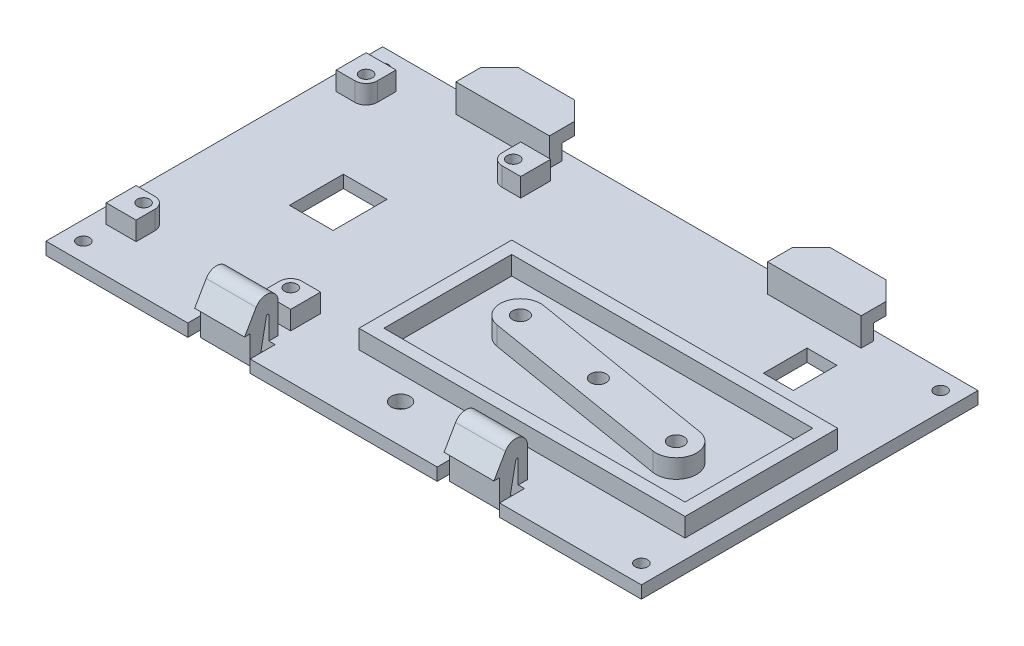
SolidWorks part; units mm, degrees
ref_plane "Front Plane" through (0, 0, 0) normal (0, 0, 1) x (1, 0, 0)
ref_plane "Top Plane" through (0, 0, 0) normal (0, 1, 0) x (1, 0, 0)
ref_plane "Right Plane" through (0, 0, 0) normal (1, 0, 0) x (0, 0, -1)
sketch "Sketch1" plane through (0, 0, 0) normal (0, 1, 0) x (1, 0, 0)
  line L1 (-47.75, 27) -> (47.75, 27)
  line L2 (-47.75, 27) -> (-47.75, -27)
  line L3 (-47.75, -27) -> (47.75, -27)
  line L4 (47.75, 27) -> (47.75, -27)
  line L5 (-47.75, 27) -> (47.75, -27) construction
  line L6 (-47.75, -27) -> (47.75, 27) construction
  point P0 (0, 0)
  dimension "D1" = 95.5
  dimension "D2" = 54
extrude "Boss-Extrude1" add sketch "Sketch1" along normal blind 2
sketch "Sketch5" plane through (0, 0, 0) normal (0, -1, 0) x (1, 0, 0)
  line L1 (-46.985, -26.185) -> (46.985, -26.185) construction
  line L2 (-46.985, -26.185) -> (-46.985, 26.185) construction
  line L3 (-46.985, 26.185) -> (46.985, 26.185) construction
  line L4 (46.985, -26.185) -> (46.985, 26.185) construction
  line L5 (-46.985, -26.185) -> (46.985, 26.185) construction
  line L6 (-46.985, 26.185) -> (46.985, -26.185) construction
  line L8 (-45.9867, -25.1841) -> (45.9867, -25.1841) construction
  line L9 (-45.9867, -25.1841) -> (-45.9867, 25.1841) construction
  line L10 (-45.9867, 25.1841) -> (45.9867, 25.1841) construction
  line L11 (45.9867, -25.1841) -> (45.9867, 25.1841) construction
  line L12 (-45.9867, -25.1841) -> (45.9867, 25.1841) construction
  line L13 (-45.9867, 25.1841) -> (45.9867, -25.1841) construction
  point P0 (0, 0)
  point P8 (0, 0)
  dimension "D1" = 93.97
  dimension "D2" = 52.37
  dimension "D3" = 91.9734
  dimension "D4" = 50.3682
sketch "Sketch2" plane through (0, 2, 0) normal (0, -1, 0) x (1, 0, 0)
  line L0 (0, 0) -> (0, -6.5874) construction
  line L1 (-32.5, -23.5) -> (-17.5, -23.5)
  line L2 (-32.5, -23.5) -> (-32.5, -25.5)
  line L3 (-32.5, -25.5) -> (-17.5, -25.5)
  line L4 (-17.5, -23.5) -> (-17.5, -25.5)
  line L5 (-32.5, -23.5) -> (-17.5, -25.5) construction
  line L6 (-32.5, -25.5) -> (-17.5, -23.5) construction
  line L7 (47.75, -27) -> (-47.75, -27) construction
  line L8 (32.5, -25.5) -> (17.5, -23.5) construction
  line L9 (32.5, -23.5) -> (17.5, -25.5) construction
  line L10 (17.5, -23.5) -> (17.5, -25.5)
  line L11 (32.5, -25.5) -> (17.5, -25.5)
  line L12 (32.5, -23.5) -> (32.5, -25.5)
  line L13 (32.5, -23.5) -> (17.5, -23.5)
  point P0 (-25, -24.5)
  point P16 (25, -24.5)
  dimension "D1" = 15
  dimension "D2" = 1.5
  dimension "D3" = 2
  dimension "D4" = 25
extrude "Boss-Extrude2" add sketch "Sketch2" against normal blind 2.5
sketch "Sketch3" plane through (0, 4.5, 0) normal (0, 1, 0) x (-1, 0, 0)
  line L0 (-32.5, -23.5) -> (-17.5, -23.5)
  line L1 (-17.5, -23.5) -> (-17.5, -30.5)
  line L2 (-17.5, -30.5) -> (-32.5, -30.5)
  line L3 (-32.5, -30.5) -> (-32.5, -23.5)
  line L4 (0, 0) -> (0, -9.2174) construction
  line L5 (17.5, -30.5) -> (32.5, -30.5)
  line L6 (17.5, -23.5) -> (17.5, -30.5)
  line L7 (32.5, -23.5) -> (17.5, -23.5)
  line L8 (32.5, -30.5) -> (32.5, -23.5)
  line L9 (-17.5, -23.5) -> (-17.5, -25.5) construction
  dimension "D1" = 7
extrude "Boss-Extrude3" add sketch "Sketch3" along normal blind 2
chamfer "Chamfer1" distance 3 angle 45 4 edges at (32.5, 5.5, -30.5) (17.5, 5.5, -30.5) (-17.5, 5.5, -30.5) (-32.5, 5.5, -30.5)
sketch "Sketch4" plane through (0, 0, 0) normal (0, -1, 0) x (1, 0, 0)
  line L0 (-47.75, 27) -> (47.75, 27) construction
  line L1 (-25, 23) -> (-15, 23)
  line L2 (-25, 23) -> (-25, 27)
  line L3 (-25, 27) -> (-15, 27)
  line L4 (-15, 23) -> (-15, 27)
  line L5 (-25, 23) -> (-15, 27) construction
  line L6 (-25, 27) -> (-15, 23) construction
  line L7 (0, 0) -> (0, 12.8978) construction
  line L8 (25, 27) -> (15, 23) construction
  line L9 (25, 23) -> (15, 27) construction
  line L10 (15, 23) -> (15, 27)
  line L11 (25, 27) -> (15, 27)
  line L12 (25, 23) -> (25, 27)
  line L13 (25, 23) -> (15, 23)
  point P0 (-20, 25)
  point P15 (20, 25)
  dimension "D1" = 10
  dimension "D2" = 4
  dimension "D3" = 20
extrude "Cut-Extrude1" cut sketch "Sketch4" against normal up to next
ref_plane "Plane1" through (-20, 0, 0) normal (1, 0, 0) x (0, 0, -1)
sketch "Sketch6" plane through (-20, 0, 0) normal (1, 0, 0) x (0, 0, -1)
  line L0 (-21.5, 2) -> (-21.5, 8.6569)
  line L1 (-27, 2) -> (27, 2) construction
  line L2 (-21.5, 8.6569) -> (-24.5, 8.6569)
  line L3 (-24.5, 8.6569) -> (-26, 6.0588)
  line L4 (-26.9, 4.5) -> (-26, 4.5)
  line L5 (-26, 4.5) -> (-26, 0)
  line L9 (-23, 7.6569) -> (-23, 2)
  line L10 (-23, 2) -> (-21.5, 2)
  line L12 (-27, 2) -> (-27, 0) construction
  line L13 (-27, 0) -> (27, 0) construction
  line L14 (-26, 6.0588) -> (-26.9, 4.5)
  line L15 (-24.5, 0) -> (-23, 7.6569)
  line L18 (-26, 0) -> (-24.5, 0)
  line L19 (-26.9, 4.5) -> (-26.9, 2) construction
  point P4 (-23, 8.6569)
  dimension "D1" = 1.5
  dimension "D2" = 60
  dimension "D3" = 1.5
  dimension "D4" = 2.5
  dimension "D5" = 1
  dimension "D6" = 0.1
  dimension "D8" = 1
extrude "Boss-Extrude4" add sketch "Sketch6" along normal mid plane 8
fillet "Fillet1" 2 edges at (-20, 8.6569, 24.5) (-20, 8.6569, 21.5) type full round first side face at (-20, 6.5785, 25.7) second side face at (-20, 5.3285, 21.5) middle face at (-20, 8.6569, 23)
fillet "Fillet2" radius 0.2 1 edges at (-20, 7.6569, 23)
mirror "Mirror1" about plane through (0, 0, 0) normal (1, 0, 0) of "Fillet2", "Fillet1", "Boss-Extrude4"
sketch "Sketch12" plane through (0, 2, 0) normal (0, 1, 0) x (1, 0, 0)
  line L0 (-47.75, -27) -> (-25, -27) construction
  line L1 (-47.75, 27) -> (-47.75, -27) construction
  line L2 (0, 6.8487) -> (0, 0) construction
  line L3 (0, 0) -> (6.5878, 0) construction
  line L6 (-45.9867, -25.1841) -> (45.9867, -25.1841) construction
  line L7 (45.9867, 25.1841) -> (45.9867, -25.1841) construction
  circle A0 centre (2.9867, -20.8641) radius 1.5
  circle A1 centre (-44.75, -24) radius 1
  circle A2 centre (44.75, -24) radius 1
  circle A3 centre (-44.75, 24) radius 1
  circle A4 centre (44.75, 24) radius 1
  dimension "D1" = 2
  dimension "D6" = 3
  dimension "D2" = 3
  dimension "D3" = 3
  dimension "D4" = 43
  dimension "D5" = 4.32
extrude "Cut-Extrude5" cut sketch "Sketch12" against normal up to next
sketch "Sketch13" plane through (0, 2, 0) normal (0, 1, 0) x (1, 0, 0)
  line L0 (45.9867, 25.1841) -> (45.9867, -25.1841) construction
  line L1 (28.1407, 19.1841) -> (32.9407, 19.1841)
  line L2 (28.1407, 19.1841) -> (28.1407, 12.1841)
  line L3 (28.1407, 12.1841) -> (32.9407, 12.1841)
  line L4 (32.9407, 19.1841) -> (32.9407, 12.1841)
  line L5 (28.1407, 19.1841) -> (32.9407, 12.1841) construction
  line L6 (28.1407, 12.1841) -> (32.9407, 19.1841) construction
  line L7 (-45.9867, 25.1841) -> (45.9867, 25.1841) construction
  point P0 (30.5407, 15.6841)
  dimension "D1" = 15.446
  dimension "D2" = 9.5
  dimension "D3" = 7
  dimension "D4" = 4.8
extrude "Cut-Extrude6" cut sketch "Sketch13" against normal up to next
sketch "Sketch8" plane through (0, 0, 0) normal (0, -1, 0) x (1, 0, 0)
  line L0 (-43.75, -17.35) -> (-43.75, -20.35) construction
  line L1 (-44.75, 19.75) -> (-16.15, 19.75) construction
  line L2 (-44.75, 19.75) -> (-44.75, -21.75) construction
  line L3 (-44.75, -21.75) -> (-16.15, -21.75) construction
  line L4 (-16.15, 19.75) -> (-16.15, -21.75) construction
  line L5 (-44.75, 19.75) -> (-16.15, -21.75) construction
  line L6 (-44.75, -21.75) -> (-16.15, 19.75) construction
  line L7 (-43.75, -20.35) -> (-40.75, -20.35) construction
  line L8 (-30.45, -6.366) -> (-30.45, -1) construction
  line L9 (-30.45, -1) -> (-27.7524, -1) construction
  line L10 (-17.15, -20.35) -> (-20.15, -20.35) construction
  line L11 (-17.15, -17.35) -> (-17.15, -20.35) construction
  line L12 (-43.75, 15.35) -> (-43.75, 18.35) construction
  line L13 (-43.75, 18.35) -> (-40.75, 18.35) construction
  line L14 (-17.15, 18.35) -> (-20.15, 18.35) construction
  line L15 (-17.15, 15.35) -> (-17.15, 18.35) construction
  line L17 (-32.7, 2) -> (-26.7, 2) construction
  line L18 (-32.7, 2) -> (-32.7, -5.65) construction
  line L19 (-32.7, -5.65) -> (-26.7, -5.65) construction
  line L20 (-26.7, 2) -> (-26.7, -5.65) construction
  line L21 (-32.7, 2) -> (-26.7, -5.65) construction
  line L22 (-32.7, -5.65) -> (-26.7, 2) construction
  line L23 (-33.2, 2.5) -> (-26.2, 2.5)
  line L24 (-33.2, 2.5) -> (-33.2, -6.15)
  line L25 (-33.2, -6.15) -> (-26.2, -6.15)
  line L26 (-26.2, 2.5) -> (-26.2, -6.15)
  line L27 (-33.2, 2.5) -> (-26.2, -6.15) construction
  line L28 (-33.2, -6.15) -> (-26.2, 2.5) construction
  line L29 (-47.75, -27) -> (-47.75, 27) construction
  circle A0 centre (-42.25, -18.85) radius 1.5 construction
  circle A11 centre (-18.65, -18.85) radius 1.5 construction
  circle A13 centre (-42.25, 16.85) radius 1.5 construction
  circle A15 centre (-18.65, 16.85) radius 1.5 construction
  point P0 (-30.45, -1)
  point P19 (-29.7, -1.825)
  point P27 (-27.7524, 0)
  point P33 (0, 0)
  point P35 (-29.7, -1.825)
  dimension "D5" = 3
  dimension "D6" = 10.55
  dimension "D1" = 28.6
  dimension "D2" = 41.5
  dimension "D3" = 1.4
  dimension "D4" = 1
  dimension "D7" = 3
  dimension "D8" = 3
  dimension "D9" = 7.65
  dimension "D10" = 6
  dimension "D11" = 16.1
  dimension "D12" = 3
  dimension "D13" = 0.5
  dimension "D14" = 0.5
  dimension "D15" = 1
extrude "Cut-Extrude2" cut sketch "Sketch8" against normal up to next
sketch "Sketch9" plane through (0, 2, 0) normal (0, 1, 0) x (1, 0, 0)
  line L0 (-27.7524, 1) -> (-30.45, 1) construction
  line L1 (-30.45, 1) -> (-30.45, 6.366) construction
  line L2 (-45.25, -15.05) -> (-45.25, -19.85)
  line L3 (-45.25, -19.85) -> (-40.45, -19.85)
  line L4 (-15.65, -15.05) -> (-18.65, -15.05)
  line L5 (-43.75, -18.35) -> (-40.75, -18.35) construction
  line L6 (-43.75, -15.35) -> (-43.75, -18.35) construction
  line L7 (-40.45, -16.85) -> (-40.45, -19.85)
  line L8 (-45.25, -15.05) -> (-42.25, -15.05)
  line L9 (-20.45, -16.85) -> (-20.45, -19.85)
  line L10 (-15.65, -19.85) -> (-20.45, -19.85)
  line L11 (-15.65, -15.05) -> (-15.65, -19.85)
  line L12 (-45.25, 17.05) -> (-42.25, 17.05)
  line L13 (-40.45, 18.85) -> (-40.45, 21.85)
  line L14 (-45.25, 21.85) -> (-40.45, 21.85)
  line L15 (-45.25, 17.05) -> (-45.25, 21.85)
  line L16 (-15.65, 17.05) -> (-15.65, 21.85)
  line L17 (-15.65, 21.85) -> (-20.45, 21.85)
  line L18 (-20.45, 18.85) -> (-20.45, 21.85)
  line L19 (-15.65, 17.05) -> (-18.65, 17.05)
  circle A0 centre (-42.25, -16.85) radius 1
  circle A1 centre (-42.25, -16.85) radius 1.5 construction
  arc A3 (-40.45, -16.85) -> (-42.25, -15.05) centre (-42.25, -16.85) ccw
  arc A4 (-20.45, -16.85) -> (-18.65, -15.05) centre (-18.65, -16.85) cw
  circle A5 centre (-18.65, -16.85) radius 1
  arc A6 (-40.45, 18.85) -> (-42.25, 17.05) centre (-42.25, 18.85) cw
  circle A7 centre (-42.25, 18.85) radius 1
  circle A8 centre (-18.65, 18.85) radius 1
  arc A9 (-20.45, 18.85) -> (-18.65, 17.05) centre (-18.65, 18.85) ccw
  dimension "D1" = 2
  dimension "D2" = 1.5
  dimension "D4" = 0.3
  dimension "D3" = 1.5
extrude "Boss-Extrude5" add sketch "Sketch9" along normal blind 3 contours L16 L17 L18 A9 L19 | L15 L14 L13 A6 L12 | L3 L7 A3 L8 L2 | L10 L9 A4 L4 L11
extrude "Cut-Extrude3" cut sketch "Sketch9<3>" along normal up to next from offset 1 contours A0 | A5 | A8 | A7
sketch "Sketch9<3>" plane through (0, 2, 0) normal (0, 1, 0) x (1, 0, 0) same geometry as "Sketch9"
sketch "Sketch10" plane through (0, 2, 0) normal (0, 1, 0) x (1, 0, 0)
  line L0 (-7.55, 5.5) -> (-5.55, 5.5) construction
  line L1 (-7.55, 7.5) -> (44.75, 7.5)
  line L2 (-7.55, 7.5) -> (-7.55, -17)
  line L3 (-7.55, -17) -> (44.75, -17)
  line L4 (44.75, 7.5) -> (44.75, -17)
  line L5 (-7.55, 7.5) -> (44.75, -17) construction
  line L6 (-7.55, -17) -> (44.75, 7.5) construction
  line L7 (47.75, -27) -> (47.75, 27) construction
  line L12 (3.6, -2.25) -> (18.6, -4.75) construction
  line L13 (18.6, -4.75) -> (33.6, -7.25) construction
  line L38 (-15, -27) -> (15, -27) construction
  line L39 (-5.55, 5.5) -> (42.75, 5.5)
  line L40 (-5.55, 5.5) -> (-5.55, -15)
  line L41 (-5.55, -15) -> (42.75, -15)
  line L42 (42.75, 5.5) -> (42.75, -15)
  line L43 (-5.55, 5.5) -> (42.75, -15) construction
  line L44 (-5.55, -15) -> (42.75, 5.5) construction
  line L45 (-5.55, 5.5) -> (-5.55, 7.5) construction
  line L46 (3.6, -2.25) -> (33.6, -7.25) construction
  line L47 (4.1343, 0.9558) -> (34.1343, -4.0442)
  line L48 (3.0657, -5.4558) -> (33.0657, -10.4558)
  circle A0 centre (18.6, -4.75) radius 1.25
  circle A2 centre (3.6, -2.25) radius 1.25
  circle A3 centre (33.6, -7.25) radius 1.25
  arc A4 (4.1343, 0.9558) -> (3.0657, -5.4558) centre (3.6, -2.25) ccw
  arc A5 (33.0657, -10.4558) -> (34.1343, -4.0442) centre (33.6, -7.25) ccw
  point P13 (18.6, -4.75)
  dimension "D4" = 2.5
  dimension "D5" = 15
  dimension "D8" = 10
  dimension "D9" = 2
  dimension "D1" = 52.3
  dimension "D2" = 24.5
  dimension "D3" = 3
  dimension "D6" = 2.5
  dimension "D7" = 2
extrude "Boss-Extrude6" add sketch "Sketch10" along normal blind 3 contours L4 L1 L2 L3 L39 L42 L41 L40 | L48 A5 L47 A4 region at (18.6, 2, -6.9225)
extrude "Cut-Extrude4" cut sketch "Sketch10<4>" along normal up to next from offset 1 contours A2 | A0 | A3
sketch "Sketch10<4>" plane through (0, 2, 0) normal (0, 1, 0) x (1, 0, 0) same geometry as "Sketch10"
